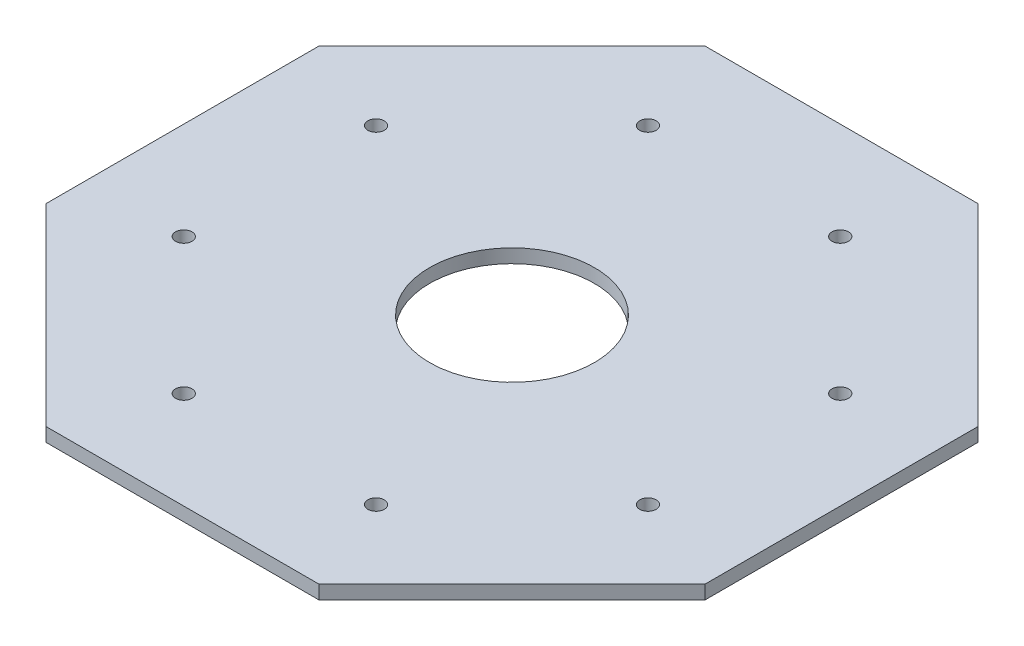
SolidWorks part; units mm, degrees
ref_plane "Front Plane" through (0, 0, 0) normal (0, 0, 1) x (1, 0, 0)
ref_plane "Top Plane" through (0, 0, 0) normal (0, 1, 0) x (1, 0, 0)
ref_plane "Right Plane" through (0, 0, 0) normal (1, 0, 0) x (0, 0, -1)
sketch "Sketch1" plane through (0, 0, 0) normal (0, 1, 0) x (1, 0, 0)
  line L0 (-2.3657, 0) -> (-2.3657, 182.3554) construction
  line L1 (63.1261, 152.4) -> (-63.1261, 152.4)
  line L2 (-63.1261, 152.4) -> (-152.4, 63.1261)
  line L3 (-152.4, 63.1261) -> (-152.4, -63.1261)
  line L4 (-152.4, -63.1261) -> (-63.1261, -152.4)
  line L5 (-63.1261, -152.4) -> (63.1261, -152.4)
  line L6 (63.1261, -152.4) -> (152.4, -63.1261)
  line L7 (152.4, -63.1261) -> (152.4, 63.1261)
  line L8 (152.4, 63.1261) -> (63.1261, 152.4)
  circle A0 centre (0, 0) radius 152.4 construction
  dimension "D1" = 304.8
extrude "Boss-Extrude1" add sketch "Sketch1" along normal blind 6.35
sketch "Sketch2" plane through (0, 6.35, 0) normal (0, 1, 0) x (1, 0, 0)
  circle A0 centre (0, 0) radius 38.1
  dimension "D1" = 76.2
extrude "Cut-Extrude1" cut sketch "Sketch2" against normal through all both and the other way through all
sketch "Sketch3" plane through (0, 6.35, 0) normal (0, 1, 0) x (1, 0, 0)
  line L0 (0, 0) -> (63.1261, -152.4) construction
  circle A0 centre (44.4634, -107.3442) radius 3.81
  circle A1 centre (-44.4634, -107.3442) radius 3.81
  circle A2 centre (-107.3442, -44.4634) radius 3.81
  circle A3 centre (-107.3442, 44.4634) radius 3.81
  circle A4 centre (-44.4634, 107.3442) radius 3.81
  circle A5 centre (44.4634, 107.3442) radius 3.81
  circle A6 centre (107.3442, 44.4634) radius 3.81
  circle A7 centre (107.3442, -44.4634) radius 3.81
  point P23 (0, 0)
  dimension "D1" = 7.62
  dimension "D2" = 48.768
  dimension "D3" = 8
extrude "Cut-Extrude2" cut sketch "Sketch3" against normal through all
